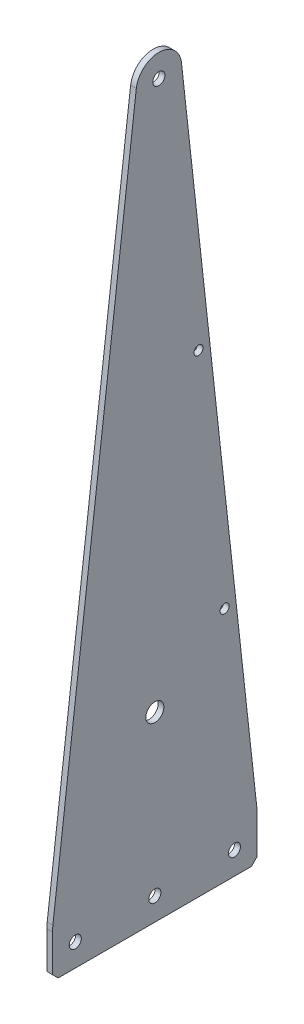
SolidWorks part; units mm, degrees
material "6061-T6 (SS)"
ref_plane "Front" through (0, 0, 0) normal (0, 0, 1) x (1, 0, 0)
ref_plane "Top" through (0, 0, 0) normal (0, 1, 0) x (1, 0, 0)
ref_plane "Right" through (0, 0, 0) normal (1, 0, 0) x (0, 0, -1)
sketch "Sketch1" plane through (0, 0, 0) normal (1, 0, 0) x (0, 0, -1)
  line L5 (82.55, 101.6) -> (-348.9452, 11.9126) construction
  line L6 (82.55, 101.6) -> (-7.1374, 533.0952) construction
  line L7 (84.8102, 406.9637) -> (41.3431, 160.4496) construction
  line L8 (41.3431, 160.4496) -> (23.7004, 60.3931) construction
  line L9 (82.55, 101.6) -> (23.7004, 60.3931) construction
  line L10 (23.7004, 60.3931) -> (17.9273, 88.168) construction
  line L11 (82.55, 101.6) -> (41.3431, 160.4496) construction
  line L12 (41.3431, 160.4496) -> (69.118, 166.2227) construction
  circle A0 centre (82.55, 101.6) radius 5.0419
  dimension "D1" = 10.0838
  dimension "D3" = 82.55
  dimension "D2" = 101.6
  dimension "D4" = 80
  dimension "D7" = 89.6874
  dimension "D8" = 431.4952
  dimension "D9" = 90
  dimension "D10" = 101.6
  dimension "D11" = 250.317
sketch "Sketch2" plane through (0, 0, 0) normal (1, 0, 0) x (0, 0, -1)
  line L0 (25.4, 0) -> (25.4, 25.4)
  line L2 (25.4, 0) -> (139.7, 0)
  line L3 (139.7, 0) -> (139.7, 25.4)
  line L4 (139.7, 25.4) -> (97.4335, 408.3569)
  line L6 (25.4, 25.4) -> (72.2039, 408.5038)
  arc A0 (97.4335, 408.3569) -> (72.2039, 408.5038) centre (84.8102, 406.9637) ccw
  circle A2 centre (82.55, 101.6) radius 5.0419 construction
  circle A3 centre (82.55, 101.6) radius 5.0419
  circle A4 centre (84.8102, 406.9637) radius 3.3782
  point P12 (0, 0)
  point P14 (18.3824, 0)
  dimension "D3" = 12.7
  dimension "D4" = 6.7564
  dimension "D5" = 25.4
  dimension "D1" = 25.4
  dimension "D2" = 139.7
extrude "Boss-Extrude2" add sketch "Sketch2" along normal blind 3.175
sketch "Sketch3" plane through (3.175, 0, 0) normal (1, 0, 0) x (0, 0, -1)
  line L0 (25.4, 0) -> (139.7, 0) construction
  line L1 (25.4, 25.4) -> (25.4, 0) construction
  line L2 (139.7, 0) -> (139.7, 25.4) construction
  line L3 (38.1, 12.7) -> (127, 12.7) construction
  line L4 (139.7, 25.4) -> (97.4335, 408.3569) construction
  line L5 (121.5193, 132.2427) -> (106.9239, 264.4854) construction
  line L6 (106.9239, 264.4854) -> (92.3284, 396.7282) construction
  line L7 (121.5193, 132.2427) -> (136.1148, 0) construction
  circle A0 centre (38.1, 12.7) radius 3.3782
  circle A1 centre (82.55, 12.7) radius 3.3782
  circle A2 centre (127, 12.7) radius 3.3782
  circle A3 centre (106.9239, 264.4854) radius 2.54
  circle A4 centre (121.5193, 132.2427) radius 2.54
  arc A5 (97.4335, 408.3569) -> (72.2039, 408.5038) centre (84.8102, 406.9637) ccw construction
  dimension "D1" = 12.7
  dimension "D2" = 12.7
  dimension "D3" = 12.7
  dimension "D4" = 6.7564
  dimension "D5" = 6.35
  dimension "D6" = 6.35
  dimension "D7" = 5.08
extrude "Cut-Extrude1" cut sketch "Sketch3" against normal through all
chamfer "Chamfer1" distance 3.175 angle 45 2 edges at (1.5875, 0, -25.4) (1.5875, 0, -139.7)
fillet "Fillet1" radius 25.4 2 edges at (1.5875, 25.4, -139.7) (1.5875, 25.4, -25.4)
